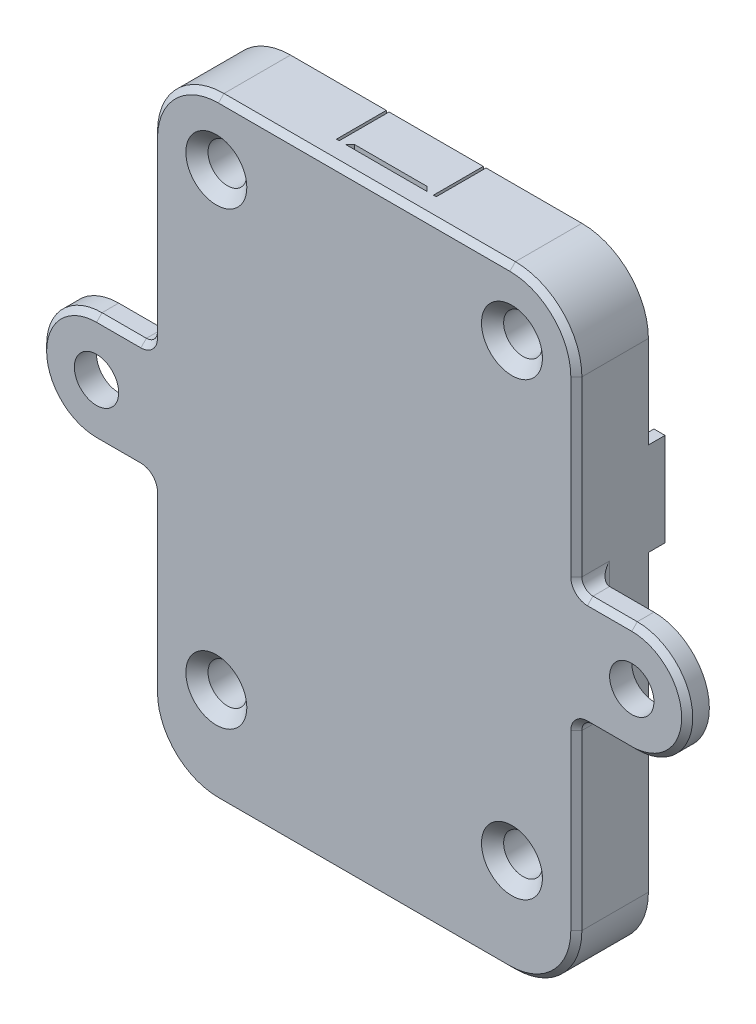
SolidWorks part; units mm, degrees
ref_plane "Front Plane" through (0, 0, 0) normal (0, 0, 1) x (1, 0, 0)
ref_plane "Top Plane" through (0, 0, 0) normal (0, 1, 0) x (1, 0, 0)
ref_plane "Right Plane" through (0, 0, 0) normal (1, 0, 0) x (0, 0, -1)
sketch "Sketch1" plane through (0, 0, 0) normal (0, 0, 1) x (1, 0, 0)
  line L0 (-4, 0) -> (-30.29, 0) construction
  line L1 (-34.29, 4) -> (-34.29, 44.26) construction
  line L2 (0, 44.26) -> (0, 4) construction
  line L3 (-30.29, 48.26) -> (-4, 48.26) construction
  line L4 (-4, 0) -> (-30.29, 0) construction
  line L5 (-34.29, 4) -> (-34.29, 44.26) construction
  line L6 (0, 44.26) -> (0, 4) construction
  line L7 (-30.29, 48.26) -> (-4, 48.26) construction
  line L8 (-30.29, 49.26) -> (-4, 49.26)
  line L9 (1, 44.26) -> (1, 4)
  line L11 (-35.29, 4) -> (-35.29, 44.26)
  line L12 (-36.29, 4) -> (-36.29, 44.26)
  line L14 (2, 44.26) -> (2, 4)
  line L15 (-30.29, 50.26) -> (-4, 50.26)
  line L16 (-4, -1) -> (-30.29, -1) construction
  line L17 (-4, -2) -> (-30.29, -2) construction
  line L18 (-4, -4) -> (-30.29, -4)
  line L19 (-17.145, 49.26) -> (-17.145, -4) construction
  line L20 (-17.145, 22.63) -> (-4, 22.63) construction
  line L21 (1, 4) -> (1, 1)
  line L22 (2, 4) -> (2, 1)
  line L23 (-4, -5) -> (-30.29, -5)
  line L24 (-36.29, 4) -> (-36.29, 1)
  line L25 (-35.29, 4) -> (-35.29, 1)
  circle A0 centre (-3.81, 44.45) radius 1.75 construction
  circle A1 centre (-30.48, 44.45) radius 1.75 construction
  circle A2 centre (-30.48, 3.81) radius 1.75 construction
  circle A3 centre (-3.81, 3.81) radius 1.75 construction
  arc A4 (-34.29, 4) -> (-30.29, 0) centre (-30.29, 4) ccw construction
  arc A5 (-4, 0) -> (0, 4) centre (-4, 4) ccw construction
  arc A6 (0, 44.26) -> (-4, 48.26) centre (-4, 44.26) ccw construction
  arc A7 (-30.29, 48.26) -> (-34.29, 44.26) centre (-30.29, 44.26) ccw construction
  circle A8 centre (-3.81, 44.45) radius 1.75
  circle A9 centre (-30.48, 44.45) radius 1.75
  circle A10 centre (-30.48, 3.81) radius 1.75
  circle A11 centre (-3.81, 3.81) radius 1.75
  arc A12 (-34.29, 4) -> (-30.29, 0) centre (-30.29, 4) ccw construction
  arc A13 (-4, 0) -> (0, 4) centre (-4, 4) ccw construction
  arc A14 (0, 44.26) -> (-4, 48.26) centre (-4, 44.26) ccw construction
  arc A15 (-30.29, 48.26) -> (-34.29, 44.26) centre (-30.29, 44.26) ccw construction
  arc A16 (1, 44.26) -> (-4, 49.26) centre (-4, 44.26) ccw
  arc A19 (-30.29, 49.26) -> (-35.29, 44.26) centre (-30.29, 44.26) ccw
  arc A20 (-30.29, 50.26) -> (-36.29, 44.26) centre (-30.29, 44.26) ccw
  arc A23 (2, 44.26) -> (-4, 50.26) centre (-4, 44.26) ccw
  arc A24 (-4, -1) -> (1, 4) centre (-4, 4) ccw construction
  arc A25 (-35.29, 4) -> (-30.29, -1) centre (-30.29, 4) ccw construction
  arc A26 (-4, -2) -> (2, 4) centre (-4, 4) ccw construction
  arc A27 (-36.29, 4) -> (-30.29, -2) centre (-30.29, 4) ccw construction
  arc A28 (-30.29, -5) -> (-36.29, 1) centre (-30.29, 1) cw
  arc A29 (-30.29, -4) -> (-35.29, 1) centre (-30.29, 1) cw
  arc A30 (2, 1) -> (-4, -5) centre (-4, 1) cw
  arc A31 (1, 1) -> (-4, -4) centre (-4, 1) cw
  dimension "D1" = 1
  dimension "D2" = 2
  dimension "D3" = 4
extrude "Boss-Extrude1" add sketch "Sketch1" against normal blind 4.5 from offset 2 contours L8 A16 L9 L21 A31 L18 A29 L25 L11 A19 | L15 A23 L14 L22 A30 L23 A28 L24 L12 A20
sketch "Sketch3" plane through (0, 0, 2) normal (0, 0, 1) x (1, 0, 0)
  line L0 (-30.29, 50.26) -> (-4, 50.26) construction
  line L1 (2, 44.26) -> (2, 1) construction
  line L3 (-36.29, 1) -> (-36.29, 44.26) construction
  line L4 (-30.29, 50.26) -> (-4, 50.26)
  line L5 (2, 44.26) -> (2, 27.63)
  line L7 (-36.29, 1) -> (-36.29, 17.63)
  line L8 (-35.29, 22.63) -> (-41.29, 22.63) construction
  line L9 (-35.29, 1) -> (-35.29, 44.26) construction
  line L10 (-41.29, 27.63) -> (-36.29, 27.63)
  line L11 (-41.29, 17.63) -> (-36.29, 17.63)
  line L12 (-36.29, 27.63) -> (-36.29, 44.26)
  line L13 (-17.145, 49.26) -> (-17.145, -4) construction
  line L14 (-30.29, 49.26) -> (-4, 49.26) construction
  line L15 (7, 17.63) -> (2, 17.63)
  line L16 (7, 27.63) -> (2, 27.63)
  line L17 (2, 17.63) -> (2, 1)
  line L18 (-4, -4) -> (-30.29, -4) construction
  line L19 (-4, -5) -> (-30.29, -5) construction
  line L20 (-4, -5) -> (-30.29, -5)
  arc A0 (-30.29, 50.26) -> (-36.29, 44.26) centre (-30.29, 44.26) ccw construction
  arc A1 (2, 44.26) -> (-4, 50.26) centre (-4, 44.26) ccw construction
  arc A4 (-30.29, 50.26) -> (-36.29, 44.26) centre (-30.29, 44.26) ccw
  arc A5 (2, 44.26) -> (-4, 50.26) centre (-4, 44.26) ccw
  circle A8 centre (-30.48, 3.81) radius 1.75 construction
  circle A9 centre (-3.81, 3.81) radius 1.75 construction
  circle A10 centre (-30.48, 44.45) radius 1.75 construction
  circle A11 centre (-3.81, 44.45) radius 1.75 construction
  circle A12 centre (-30.48, 3.81) radius 1.75
  circle A13 centre (-3.81, 3.81) radius 1.75
  circle A14 centre (-3.81, 44.45) radius 1.75
  circle A15 centre (-30.48, 44.45) radius 1.75
  circle A16 centre (-41.29, 22.63) radius 2
  arc A17 (-41.29, 27.63) -> (-41.29, 17.63) centre (-41.29, 22.63) ccw
  arc A18 (7, 27.63) -> (7, 17.63) centre (7, 22.63) cw
  circle A19 centre (7, 22.63) radius 2
  arc A20 (-36.29, 1) -> (-30.29, -5) centre (-30.29, 1) ccw construction
  arc A21 (-4, -5) -> (2, 1) centre (-4, 1) ccw construction
  arc A22 (-36.29, 1) -> (-30.29, -5) centre (-30.29, 1) ccw
  arc A23 (-4, -5) -> (2, 1) centre (-4, 1) ccw
  dimension "D1" = 4
  dimension "D2" = 10
extrude "Boss-Extrude3" add sketch "Sketch3" along normal blind 2
fillet "Fillet1" radius 1 4 edges at (-36.29, 27.63, 3) (-36.29, 17.63, 3) (2, 27.63, 3) (2, 17.63, 3)
fillet "Fillet2" radius 1 2 edges at (-36.29, 22.63, 2) (2, 22.63, 2)
chamfer "Chamfer1" distance 1 angle 45 4 edges at (-2.06, 44.45, 4) (-28.73, 44.45, 4) (-28.73, 3.81, 4) (-2.06, 3.81, 4)
chamfer "Chamfer2" distance 0.5 angle 45 20 edges at (-17.145, 50.26, 4) (-34.5326, 48.5026, 4) (0.2426, 48.5026, 4) (-36.29, 36.445, 4) (2, 36.445, 4) (-36.5829, 27.9229, 4) (2.2929, 27.9229, 4) (-39.29, 27.63, 4) (5, 27.63, 4) (-46.29, 22.63, 4) (12, 22.63, 4) (-39.29, 17.63, 4) (5, 17.63, 4) (-36.5829, 17.3371, 4) (2.2929, 17.3371, 4) (-36.29, 8.815, 4) (2, 8.815, 4) (-34.5326, -3.2426, 4) (0.2426, -3.2426, 4) (-17.145, -5, 4)
sketch "Sketch7" plane through (0, 0, -2.5) normal (0, 0, -1) x (-1, 0, 0)
  line L0 (-2, 31.74) -> (-1, 31.74) construction
  line L1 (-2, 44.26) -> (-2, 1) construction
  line L2 (-1, 44.26) -> (-1, 1) construction
  line L3 (3.61, 35.44) -> (-0.94, 35.44) construction
  line L4 (-2, 27.54) -> (-1, 27.54)
  line L5 (-2, 27.54) -> (-2, 35.94)
  line L6 (-2, 35.94) -> (-1, 35.94)
  line L7 (-1, 27.54) -> (-1, 35.94)
  line L8 (-2, 27.54) -> (-1, 35.94) construction
  line L9 (-2, 35.94) -> (-1, 27.54) construction
  line L10 (3.61, 28.04) -> (-0.94, 28.04) construction
  point P6 (-1.5, 31.74)
  dimension "D1" = 0.5
  dimension "D2" = 0.5
extrude "Boss-Extrude4" add sketch "Sketch7" along normal blind 1.5
sketch "Sketch9" plane through (0, 0, 2) normal (0, 0, -1) x (-1, 0, 0)
  line L0 (4, -4) -> (30.29, -4) construction
  line L1 (30.29, 49.26) -> (4, 49.26) construction
  line L2 (4, -4) -> (7.56, -4)
  line L3 (7.56, 49.26) -> (4, 49.26)
  line L4 (7.56, 3.81) -> (7.56, -4)
  line L5 (-1, 44.26) -> (-1, 1) construction
  line L7 (-1, 44.26) -> (-1, 40.7)
  line L8 (7.56, 44.45) -> (7.56, 49.26)
  line L9 (3.81, 40.7) -> (-1, 40.7)
  line L10 (3.81, 7.56) -> (-1, 7.56)
  line L11 (-1, 7.56) -> (-1, 1)
  line L12 (17.145, -4) -> (17.145, 49.26) construction
  line L13 (30.29, 49.26) -> (4, 49.26) construction
  line L14 (35.29, 7.56) -> (35.29, 1)
  line L15 (30.48, 7.56) -> (35.29, 7.56)
  line L16 (30.48, 40.7) -> (35.29, 40.7)
  line L17 (26.73, 44.45) -> (26.73, 49.26)
  line L18 (35.29, 44.26) -> (35.29, 40.7)
  line L19 (26.73, 3.81) -> (26.73, -4)
  line L20 (26.73, 49.26) -> (30.29, 49.26)
  line L21 (30.29, -4) -> (26.73, -4)
  circle A0 centre (3.81, 3.81) radius 1.75 construction
  circle A2 centre (30.48, 44.45) radius 1.75 construction
  circle A3 centre (3.81, 3.81) radius 1.75
  circle A5 centre (30.48, 44.45) radius 1.75
  circle A6 centre (3.81, 44.45) radius 1.75 construction
  circle A7 centre (3.81, 44.45) radius 1.75
  arc A9 (-1, 1) -> (4, -4) centre (4, 1) ccw construction
  arc A10 (7.56, 3.81) -> (3.81, 7.56) centre (3.81, 3.81) ccw
  arc A11 (4, 49.26) -> (-1, 44.26) centre (4, 44.26) ccw construction
  arc A13 (-1, 1) -> (4, -4) centre (4, 1) ccw
  arc A15 (4, 49.26) -> (-1, 44.26) centre (4, 44.26) ccw
  arc A16 (3.81, 40.7) -> (7.56, 44.45) centre (3.81, 44.45) ccw
  arc A17 (30.48, 40.7) -> (26.73, 44.45) centre (30.48, 44.45) cw
  circle A18 centre (3.81, 44.45) radius 3.75 construction
  circle A19 centre (3.81, 3.81) radius 3.75 construction
  arc A20 (30.29, 49.26) -> (35.29, 44.26) centre (30.29, 44.26) cw
  arc A21 (35.29, 1) -> (30.29, -4) centre (30.29, 1) cw
  arc A22 (26.73, 3.81) -> (30.48, 7.56) centre (30.48, 3.81) cw
  circle A23 centre (30.48, 44.45) radius 1.75
  circle A24 centre (30.48, 3.81) radius 1.75
  point P20 (7.56, 3.81)
  point P30 (7.56, 44.45)
  arc M14 (35.29, 44.26) -> (30.29, 49.26) centre (30.29, 44.26) ccw
  line M15 (30.29, 49.26) -> (4, 49.26)
  arc M16 (4, 49.26) -> (-1, 44.26) centre (4, 44.26) ccw
  line M17 (-1, 44.26) -> (-1, 1)
  arc M18 (-1, 1) -> (4, -4) centre (4, 1) ccw
  line M19 (4, -4) -> (30.29, -4)
  arc M20 (30.29, -4) -> (35.29, 1) centre (30.29, 1) ccw
  line M21 (35.29, 1) -> (35.29, 44.26)
  circle M22 centre (30.48, 44.45) radius 1.75
  circle M23 centre (3.81, 44.45) radius 1.75
  circle M24 centre (3.81, 3.81) radius 1.75
  circle M25 centre (30.48, 3.81) radius 1.75
  dimension "D1" = 2
  dimension "D2" = 2
extrude "Boss-Extrude5" add sketch "Sketch9" along normal blind 2 contours L9 A16 L8 M15 M16 M17 M23 | A17 L16 L17 M21 M14 M15 M22 | A22 L19 L15 M19 M20 M21 M25 | L4 A10 L10 M17 M18 M19 M24 region at (-3.2983, 1.6635, 2) region at (-30.9917, 1.6635, 2) region at (0.8789, 42.48, 2) region at (-32.885, 40.8211, 2)
sketch "Sketch10" plane through (0, 0, -2.5) normal (0, 0, -1) x (-1, 0, 0)
  line L0 (17.145, 49.26) -> (17.145, 50.26) construction
  line L1 (26.73, 49.26) -> (7.56, 49.26) construction
  line L2 (30.29, 50.26) -> (4, 50.26) construction
  line L3 (30.29, 49.26) -> (4, 49.26) construction
  line L5 (21.645, 50.26) -> (21.645, 49.26)
  line L7 (12.645, 50.26) -> (12.645, 49.26)
  line L8 (21.645, 50.26) -> (12.645, 49.26) construction
  line L9 (21.645, 49.26) -> (12.645, 50.26) construction
  line L10 (12.895, 50.26) -> (12.895, 49.26)
  line L11 (21.395, 50.26) -> (21.395, 49.26)
  line L12 (12.645, 50.26) -> (12.895, 50.26)
  line L13 (12.895, 49.26) -> (12.645, 49.26)
  line L14 (21.395, 50.26) -> (21.645, 50.26)
  line L15 (21.645, 49.26) -> (21.395, 49.26)
  point P6 (17.145, 49.76)
  line M9 (30.29, 50.26) -> (4, 50.26)
  line M15 (4, 49.26) -> (30.29, 49.26)
  dimension "D1" = 9
  dimension "D2" = 0.25
  dimension "D3" = 0.25
extrude "Cut-Extrude1" cut sketch "Sketch10" against normal up to surface (4.5 mm away) contours L11 L5 M9 M15 | L10 L13 L7 L12 region at (-21.52, 49.76, -2.5) up to face at (-17.145, 23.755, 2)
sketch "Sketch11" plane through (0, 0, -2.5) normal (0, 0, -1) x (-1, 0, 0)
  line L8 (13.395, 50.26) -> (13.395, 49.26)
  line L9 (13.395, 50.26) -> (13.395, 49.26)
  line L10 (13.395, 50.26) -> (20.895, 50.26)
  line L11 (20.895, 50.26) -> (20.895, 49.26)
  line L12 (20.895, 50.26) -> (20.895, 49.26)
  line L13 (20.895, 49.26) -> (13.395, 49.26)
  dimension "D1" = 0.5
  dimension "D2" = 0.5
extrude "Cut-Extrude2" cut sketch "Sketch11" against normal up to surface (0.4 mm away) from offset 4.1 up to face at (-39.29, 22.63, 2) offset against normal yes
chamfer "Chamfer3" distance 0.5 angle 45 2 edges at (-13.395, 49.76, 1.6) (-20.895, 49.76, 1.6)
sketch "Sketch13" plane through (0, 0, 0) normal (0, 0, -1) x (-1, 0, 0)
  line L0 (7.56, -0.5) -> (4, -0.5)
  line L1 (7.56, 3.81) -> (7.56, -4) construction
  line L3 (-1, 27.54) -> (-1, 1) construction
  line L4 (4, -4) -> (30.29, -4) construction
  line L5 (-1, 1.9384) -> (-1, 1)
  line L6 (4, -4) -> (7.56, -4)
  line L7 (35.29, 1.9384) -> (34.79, 1.9384)
  line L8 (4, 0) -> (30.29, 0) construction
  line L9 (17.145, 48.26) -> (17.145, -12.2269) construction
  line L10 (-1, 1.9384) -> (-0.5, 1.9384)
  line L11 (30.29, 48.26) -> (4, 48.26) construction
  line L12 (7.56, -4) -> (26.73, -4)
  line L13 (7.56, -0.5) -> (26.73, -0.5)
  line L14 (30.29, -4) -> (26.73, -4)
  line L15 (35.29, 1.9384) -> (35.29, 1)
  line L16 (26.73, -0.5) -> (30.29, -0.5)
  arc A0 (-1, 1) -> (4, -4) centre (4, 1) ccw construction
  arc A1 (-1, 1) -> (4, -4) centre (4, 1) ccw
  arc A2 (4, -0.5) -> (-0.5, 1.9384) centre (4, 4.8715) cw
  arc A3 (30.29, -0.5) -> (34.79, 1.9384) centre (30.29, 4.8715) ccw
  arc A4 (35.29, 1) -> (30.29, -4) centre (30.29, 1) cw
  point P19 (4, 0)
  point P30 (17.145, -0.5)
  point P31 (17.145, -4)
  point P33 (30.29, 0)
  line M12 (7.56, -4) -> (7.56, 3.81)
  line M15 (-1, 7.56) -> (-1, 1)
  arc M16 (-1, 1) -> (4, -4) centre (4, 1) ccw
  line M17 (4, -4) -> (7.56, -4)
  dimension "D1" = 0.5
  dimension "D2" = 0.5
extrude "Boss-Extrude6" add sketch "Sketch13" along normal blind 1 and the other way up to surface (2 mm away) contours L13 L9 L12 L14 A4 L15 L7 A3 L16 | L0 A2 L10 M15 M16 M17 M12 | L9 L13 L12 M12 | A4 L15 L7 A3 L16 L13 L0 A2 L10 L5 A1 L6 L12 L14 region at (-3.3921, -1.736, 0) region at (-12.3525, -2.25, 0) region at (-26.0965, -2.0114, 0) other way up to face at (-39.29, 22.63, 2)
sketch "Sketch17" plane through (0, 0, 2) normal (0, 0, -1) x (-1, 0, 0)
  line L0 (17.145, -0.5) -> (17.145, 49.26) construction
  line L1 (4, -0.5) -> (30.29, -0.5) construction
  line L2 (21.395, 49.26) -> (12.895, 49.26) construction
  line L3 (7.56, -0.5) -> (26.73, -0.5) construction
  line L4 (24.145, 7.5) -> (10.145, 7.5)
  line L5 (24.145, 7.5) -> (24.145, -0.5)
  line L6 (24.145, -0.5) -> (10.145, -0.5)
  line L7 (10.145, 7.5) -> (10.145, -0.5)
  line L8 (24.145, 7.5) -> (10.145, -0.5) construction
  line L9 (24.145, -0.5) -> (10.145, 7.5) construction
  line L10 (-1, 22.0158) -> (-1, -6.453) construction
  line L11 (-1, 40.7) -> (-1, 7.56) construction
  line L12 (17.145, -0.5) -> (-13.3469, -0.5) construction
  line L13 (17.28, 15.24) -> (14.78, 15.24) construction
  line L14 (17.28, 15.24) -> (17.28, 17.6094) construction
  line L15 (1, 39.37) -> (34.29, 39.37) construction
  line L16 (16, 31.75) -> (8.38, 31.75) construction
  line L17 (35.29, 40.7) -> (35.29, 7.56) construction
  line L18 (1, 38.37) -> (34.29, 38.37)
  line L19 (1, 40.7) -> (34.29, 40.7)
  line L20 (1, 40.7) -> (1, 38.37)
  line L21 (34.29, 40.7) -> (34.29, 38.37)
  line L22 (1, 24.13) -> (34.29, 24.13) construction
  line L23 (17.145, 64) -> (17.145, 14.24) construction
  line L24 (34.29, 22.8) -> (34.29, 25.13)
  line L25 (1, 22.8) -> (1, 25.13)
  line L26 (1, 22.8) -> (34.29, 22.8)
  line L27 (1, 25.13) -> (34.29, 25.13)
  line L28 (3.81, 40.7) -> (-1, 40.7) construction
  circle A0 centre (17.28, 15.24) radius 6 construction
  circle A1 centre (14.78, 15.24) radius 1.25
  circle A2 centre (19.78, 15.24) radius 1.25
  point P6 (17.145, 3.5)
  point P19 (-1, -0.5)
  point P26 (16, 31.75)
  dimension "D5" = 12
  dimension "D7" = 2.5
  dimension "D1" = 14
  dimension "D2" = 8
  dimension "D3" = 18.28
  dimension "D4" = 15.74
  dimension "D6" = 2.5
  dimension "D8" = 17
  dimension "D9" = 32.25
  dimension "D10" = 2
  dimension "D11" = 1
  dimension "D12" = 7.62
  dimension "D13" = 1
extrude "Cut-Extrude3" cut sketch "Sketch17" against normal blind 1
